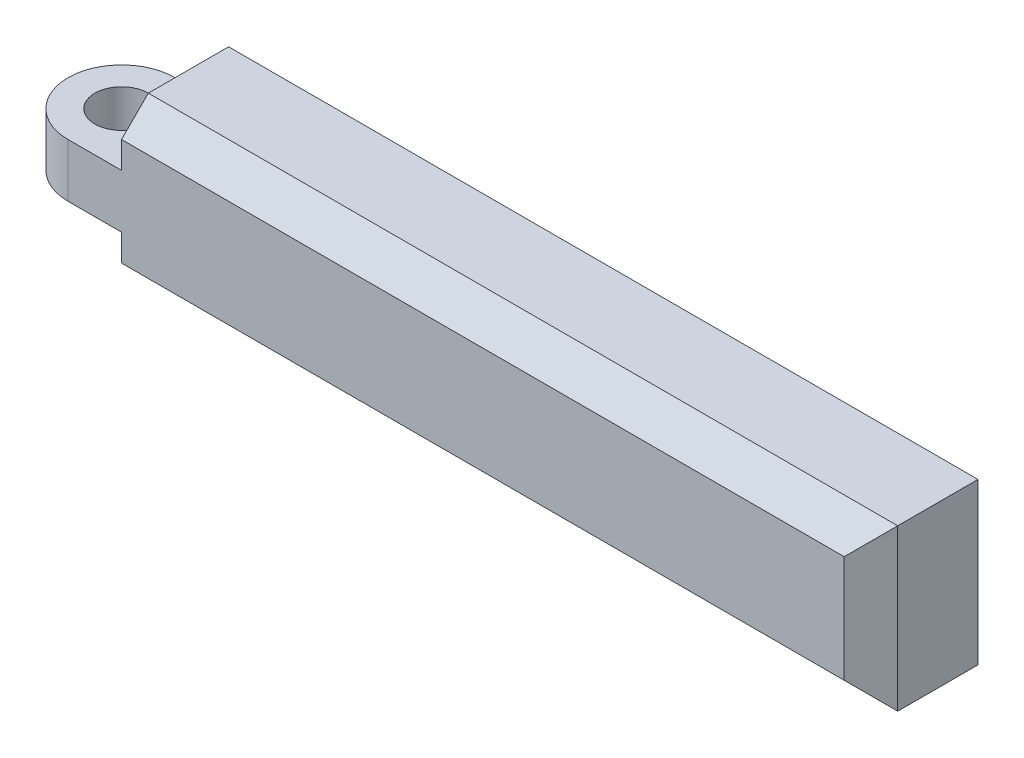
SolidWorks part; units mm, degrees
ref_plane "Front Plane" through (0, 0, 0) normal (0, 0, 1) x (1, 0, 0)
ref_plane "Top Plane" through (0, 0, 0) normal (0, 1, 0) x (1, 0, 0)
ref_plane "Right Plane" through (0, 0, 0) normal (1, 0, 0) x (0, 0, -1)
sketch "Sketch1" plane through (0, 0, 0) normal (0, 1, 0) x (1, 0, 0)
  line L1 (-7, 1) -> (7, 1)
  line L2 (-7, 1) -> (-7, -1)
  line L3 (-7, -1) -> (7, -1)
  line L4 (7, 1) -> (7, -1)
  line L5 (-7, 1) -> (7, -1) construction
  line L6 (-7, -1) -> (7, 1) construction
  point P0 (0, 0)
  dimension "D1" = 14
  dimension "D2" = 2
extrude "Boss-Extrude1" add sketch "Sketch1" along normal blind 3
chamfer "Chamfer1" distance 0.5 angle 45 3 edges at (0, 0, -1) (7, 1.5, -1) (0, 3, -1)
sketch "Sketch2" plane through (-7, 0, 0) normal (-1, 0, 0) x (0, 0, 1)
  line L0 (1, 3) -> (1, 0) construction
  line L1 (-1, 1) -> (1, 1)
  line L2 (-1, 1) -> (-1, 2)
  line L3 (-1, 2) -> (1, 2)
  line L4 (1, 1) -> (1, 2)
  line L5 (-1, 1) -> (1, 2) construction
  line L6 (-1, 2) -> (1, 1) construction
  point P0 (0, 1.5)
  point P8 (1, 1.5)
  dimension "D1" = 1
extrude "Boss-Extrude2" add sketch "Sketch2" along normal blind 2
sketch "Sketch3" plane through (0, 2, 0) normal (0, 1, 0) x (1, 0, 0)
  line L0 (-9, -1) -> (-7, -1) construction
  line L1 (-9, -1) -> (-9, 1) construction
  line L6 (-7, -1) -> (-7, 1)
  line L7 (-7, 1) -> (-9, 1)
  line L8 (-9, 1) -> (-9, -1)
  line L9 (-9, -1) -> (-7, -1)
  line L10 (-7, -1) -> (-7, 1)
  line L11 (-7, 1) -> (-9, 1)
  line L12 (-9, 1) -> (-9, -1)
  line L13 (-9, -1) -> (-7, -1)
  circle A0 centre (-8, 0) radius 1
  circle A1 centre (-8, 0) radius 0.5
  point P4 (-8, -1)
  point P7 (-9, 0)
  line M7 (-9, 1) -> (-9, -1)
  line M8 (-9, -1) -> (-7, -1)
  dimension "D1" = 2
  dimension "D2" = 0.5
  dimension "D3" = 0
extrude "Cut-Extrude1" cut sketch "Sketch3" against normal blind 2 contours A1 | A0 L11 M7 | A0 L12 M8 region at (-8.7766, 2, 0.7766) region at (-8.7766, 2, -0.7766) region at (-8, 2, 0)
mirror "Mirror1" about plane through (-7, 3, -1) normal (0, 0, 1) of bodies 103
delete or keep bodies "Body-Delete/Keep 1" type delete bodies bodies 103
